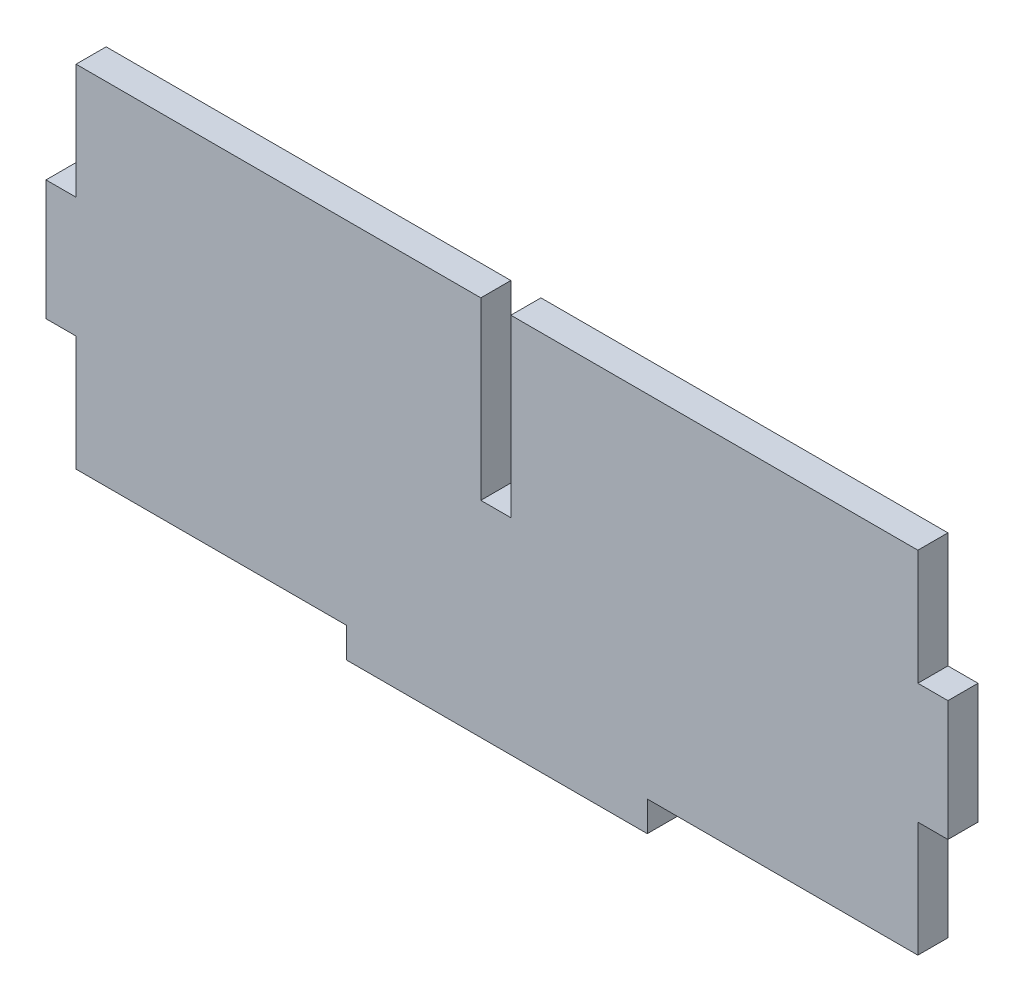
SolidWorks part; units mm, degrees
ref_plane "Front Plane" through (0, 0, 0) normal (0, 0, 1) x (1, 0, 0)
ref_plane "Top Plane" through (0, 0, 0) normal (0, 1, 0) x (1, 0, 0)
ref_plane "Right Plane" through (0, 0, 0) normal (1, 0, 0) x (0, 0, -1)
sketch "Sketch1" plane through (0, 0, 0) normal (0, 0, 1) x (1, 0, 0)
  line L0 (-42, -19) -> (-42, -4.5)
  line L1 (-45, -19) -> (45, -19)
  line L2 (-45, -19) -> (-45, 19)
  line L3 (-45, 19) -> (45, 19)
  line L4 (45, -19) -> (45, 19)
  line L5 (-45, -19) -> (45, 19) construction
  line L6 (-45, 19) -> (45, -19) construction
  line L7 (-42, -4.5) -> (-45, -4.5)
  line L8 (-45, 7.5) -> (-42, 7.5)
  line L9 (45, -4.5) -> (42, -4.5)
  line L10 (42, -4.5) -> (42, -19)
  line L11 (-42, 7.5) -> (-42, 19)
  line L12 (45, 7.5) -> (42, 7.5)
  line L13 (42, 7.5) -> (42, 19)
  line L14 (-45, -16) -> (-15, -16)
  line L15 (-15, -16) -> (-15, -19)
  line L16 (45, -16) -> (15, -16)
  line L17 (15, -16) -> (15, -19)
  line L19 (-1.613, 1.5) -> (1.387, 1.5)
  line L20 (-1.613, 1.5) -> (-1.613, 19)
  line L21 (-1.613, 19) -> (1.387, 19)
  line L22 (1.387, 1.5) -> (1.387, 19)
  line L23 (-1.613, 1.5) -> (1.387, 19) construction
  line L24 (-1.613, 19) -> (1.387, 1.5) construction
  point P0 (0, 0)
  point P23 (-0.113, 10.25)
  dimension "D1" = 90
  dimension "D2" = 38
  dimension "D3" = 11.5
  dimension "D4" = 30
  dimension "D5" = 3
  dimension "D6" = 12
  dimension "D7" = 30
  dimension "D8" = 3
  dimension "D9" = 17.5
  dimension "D10" = 3
  dimension "D11" = 12
  dimension "D12" = 14.5
extrude "Boss-Extrude1" add sketch "Sketch1" along normal blind 3 contours L3 L2 L1 L10 L9 L4 region at (0.0019, 0.7886, 0)
